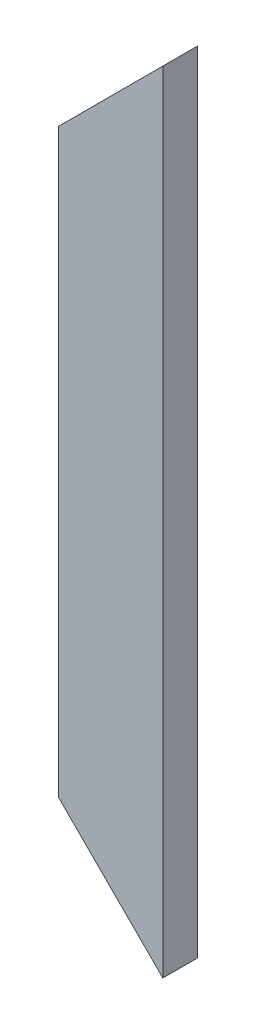
SolidWorks part; units mm, degrees
note: '?' marks a value the reader was unsure of.
material "A500"
ref_plane "Front Plane" through (0, 0, 0) normal (0, 0, 1) x (1, 0, 0)
ref_plane "Top Plane" through (0, 0, 0) normal (0, 1, 0) x (1, 0, 0)
ref_plane "Right Plane" through (0, 0, 0) normal (1, 0, 0) x (0, 0, -1)
sketch "Sketch1" plane through (0, 0, 0) normal (0, 1, 0) x (1, 0, 0)
  line L0 (0, 9.652) -> (0, 12.7) construction
  line L1 (-38.1, 12.7) -> (38.1, 12.7)
  line L2 (-38.1, 12.7) -> (-38.1, -12.7)
  line L3 (-38.1, -12.7) -> (38.1, -12.7)
  line L4 (38.1, 12.7) -> (38.1, -12.7)
  line L5 (-35.052, 9.652) -> (35.052, 9.652)
  line L6 (-35.052, 9.652) -> (-35.052, -9.652)
  line L7 (-35.052, -9.652) -> (35.052, -9.652)
  line L8 (35.052, 9.652) -> (35.052, -9.652)
  line L9 (35.052, 0) -> (38.1, 0) construction
  line L10 (0, -9.652) -> (0, -12.7) construction
  line L11 (-35.052, 0) -> (-38.1, 0) construction
  line L12 (0, 9.652) -> (0, 0) construction
  line L13 (0, 0) -> (-35.052, 0) construction
  dimension "D1" = 76.2
  dimension "D2" = 25.4
  dimension "D3" = 3.048
extrude "Boss-Extrude1" add sketch "Sketch1" along normal up to vertex (500 mm away)
ref_plane "Plane1" through (0, 0, 0) normal (0, 0, 1) x (1, 0, 0)
sketch "Sketch2" plane through (0, 0, 0) normal (0, 0, 1) x (1, 0, 0)
  line L0 (0, 0) -> (0, 500) construction
  line L1 (-38.1, 500) -> (38.1, 500) construction
  line L2 (0, 250) -> (-38.1, 250) construction
  line L3 (-38.1, 500) -> (-38.1, 0) construction
  line L4 (0, 250) -> (38.1, 250) construction
  line L5 (38.1, 500) -> (38.1, 0) construction
ref_axis "Axis1" through (0, 500, 0) along (0, -1, 0)?
sketch "Sketch3" plane through (0, 0, 0) normal (0, -1, 0) x (1, 0, 0)
  line L0 (-35.052, -9.652) -> (-35.052, 9.652) construction
  line L1 (-35.052, 9.652) -> (35.052, 9.652) construction
  line L2 (35.052, 9.652) -> (35.052, -9.652) construction
  line L3 (35.052, -9.652) -> (-35.052, -9.652) construction
  line L4 (-38.1, 12.7) -> (-38.1, -12.7)
  line L5 (-38.1, -12.7) -> (38.1, -12.7)
  line L6 (38.1, -12.7) -> (38.1, 12.7)
  line L7 (38.1, 12.7) -> (-38.1, 12.7)
  line L8 (-38.1, 12.7) -> (-38.1, -12.7)
  line L9 (-38.1, -12.7) -> (38.1, -12.7)
  line L10 (38.1, -12.7) -> (38.1, 12.7)
  line L11 (38.1, 12.7) -> (-38.1, 12.7)
  line L12 (-35.052, -9.652) -> (-35.052, 9.652)
  line L13 (-35.052, 9.652) -> (35.052, 9.652)
  line L14 (35.052, 9.652) -> (35.052, -9.652)
  line L15 (35.052, -9.652) -> (-35.052, -9.652)
  dimension "D1" = 0
extrude "Boss-Extrude2" add sketch "Sketch3" along normal blind 38.1
sketch "Sketch4" plane through (0, 500, 0) normal (0, 1, 0) x (1, 0, 0)
  line L0 (-35.052, 9.652) -> (-35.052, -9.652) construction
  line L1 (35.052, 9.652) -> (-35.052, 9.652) construction
  line L2 (35.052, -9.652) -> (35.052, 9.652) construction
  line L3 (-35.052, -9.652) -> (35.052, -9.652) construction
  line L4 (-38.1, 12.7) -> (-38.1, -12.7)
  line L5 (-38.1, -12.7) -> (38.1, -12.7)
  line L6 (38.1, -12.7) -> (38.1, 12.7)
  line L7 (38.1, 12.7) -> (-38.1, 12.7)
  line L8 (-38.1, 12.7) -> (-38.1, -12.7)
  line L9 (-38.1, -12.7) -> (38.1, -12.7)
  line L10 (38.1, -12.7) -> (38.1, 12.7)
  line L11 (38.1, 12.7) -> (-38.1, 12.7)
  line L12 (-35.052, 9.652) -> (-35.052, -9.652)
  line L13 (35.052, 9.652) -> (-35.052, 9.652)
  line L14 (35.052, -9.652) -> (35.052, 9.652)
  line L15 (-35.052, -9.652) -> (35.052, -9.652)
  dimension "D1" = 0
extrude "Boss-Extrude3" add sketch "Sketch4" along normal blind 38.1
sketch "Sketch5" plane through (0, 0, 0) normal (0, 0, 1) x (1, 0, 0)
  line L0 (-62.7727, 62.7727) -> (63.0307, -63.0307)
  line L1 (0, 25.4) -> (-62.7727, 62.7727) construction
  line L2 (0, 0) -> (0, 500) construction
  line L3 (-62.7727, 62.7727) -> (-25.4, 0) construction
  line L4 (0.0477, 0) -> (-502.9523, 0) construction
  line L6 (-62.7727, 62.7727) -> (-217.2878, -60.5812)
  line L7 (-217.2878, -60.5812) -> (-91.4844, -186.3846)
  line L8 (-91.4844, -186.3846) -> (63.0307, -63.0307)
  dimension "D1" = 25.4
  dimension "D2" = 25.4
extrude "Cut-Extrude1" cut sketch "Sketch5" against normal through all both and the other way through all
sketch "Sketch6" plane through (0, 0, 0) normal (0, 0, -1) x (0, 1, 0)
  line L0 (393.891, -106.109) -> (558.8559, 58.8559)
  line L1 (393.891, -106.109) -> (424.6, 0) construction
  line L2 (0, 0) -> (500, 0) construction
  line L3 (393.891, -106.109) -> (500, -75.4) construction
  line L4 (500, 0) -> (500, -445.4) construction
  line L5 (558.8559, 58.8559) -> (555.0161, -106.109)
  line L6 (555.0161, -106.109) -> (393.891, -106.109)
  line L7 (424.6, 0) -> (500, 0) construction
  line L8 (500, 0) -> (500, -75.4) construction
extrude "Cut-Extrude2" cut sketch "Sketch6" against normal through all both and the other way through all
equation "\"tubeMainWidth\"= 76.2mm"
equation "\"tubeSecondWidth\"= 25.4mm"
equation "\"tubeThickness\"= 3.048mm"
equation "\"halfMainWidthOfTubing\"= (\"tubeMainWidth\"/2)"
equation "\"D1@Sketch1\"=\"tubeMainWidth\""
equation "\"D2@Sketch1\"=\"tubeSecondWidth\""
equation "\"D3@Sketch1\"=\"tubeThickness\""
equation "\"D1@Boss-Extrude2\"=\"halfMainWidthOfTubing\""
equation "\"D1@Boss-Extrude3\"=\"halfMainWidthOfTubing\""
